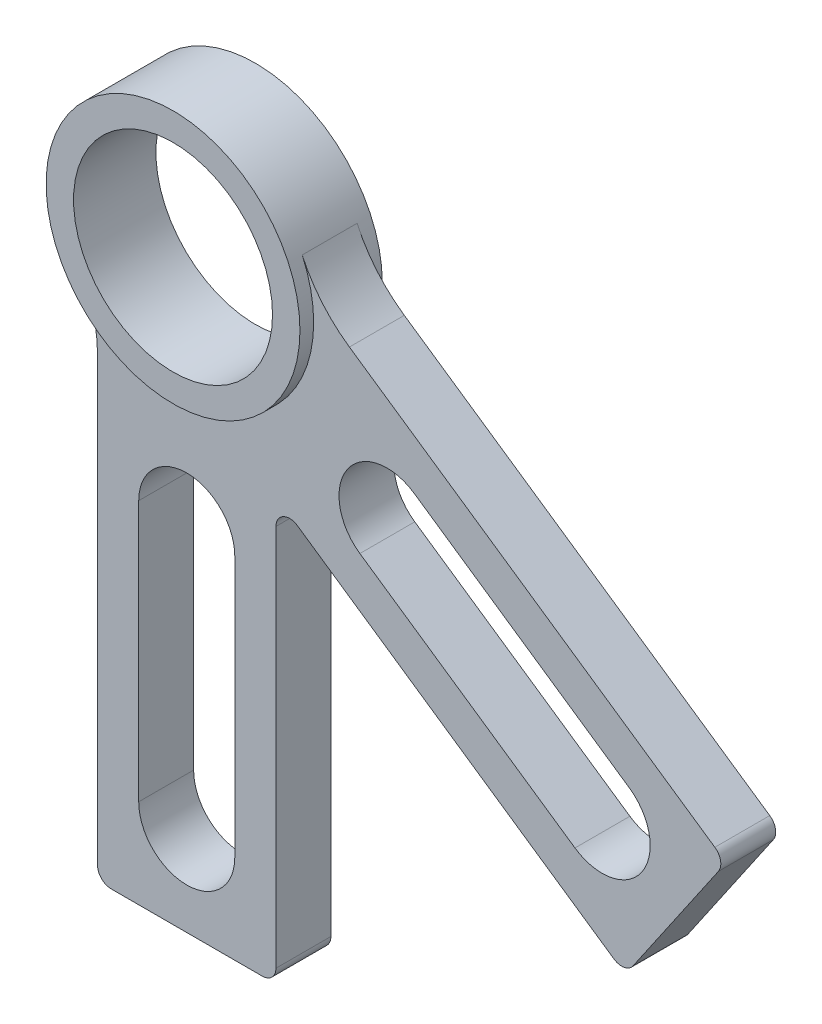
SolidWorks part; units mm, degrees
material "AISI 4130 Steel, annealed at 865C"
ref_plane "X-Y Datum" through (0, 0, 0) normal (0, 0, 1) x (1, 0, 0)
ref_plane "X-Z Datum" through (0, 0, 0) normal (0, 1, 0) x (1, 0, 0)
ref_plane "Y-Z Datum" through (0, 0, 0) normal (1, 0, 0) x (0, 0, -1)
sketch "Sketch1" plane through (0, 0, 0) normal (0, 0, 1) x (1, 0, 0)
  line L0 (0, -58.1206) -> (0, -27.9581) construction
  line L1 (-5.5562, -58.1206) -> (-5.5562, -27.9581)
  line L2 (5.5562, -58.1206) -> (5.5562, -27.9581)
  line L3 (48.0436, -32.9331) -> (23.1651, -15.8793) construction
  line L4 (44.9021, -37.516) -> (20.0236, -20.4622)
  line L5 (51.1851, -28.3502) -> (26.3066, -11.2964)
  line L6 (-10.3187, -15.7343) -> (-10.3187, -68.4393)
  line L7 (-10.3187, -68.4393) -> (10.3187, -68.4393)
  line L10 (50.7205, -47.2784) -> (62.3889, -30.2562)
  line L11 (62.3889, -30.2562) -> (18.8122, -0.3851)
  line L12 (0, -58.1206) -> (0, 0) construction
  line L13 (0, 0) -> (48.0436, -32.9331) construction
  line L14 (0, -63.6768) -> (0, -68.4393) construction
  line L15 (52.6265, -36.0746) -> (56.5547, -38.7673) construction
  line L16 (38.7458, -19.8233) -> (41.4385, -15.8951) construction
  line L17 (-5.5562, -43.0393) -> (-10.3187, -43.0393) construction
  line L18 (-10.3187, -17.6393) -> (10.3187, -17.6393) construction
  line L19 (10.3187, -17.6393) -> (10.3187, -68.4393) construction
  line L20 (5.5562, -43.0393) -> (10.3187, -43.0393) construction
  line L21 (0, -22.4018) -> (0, -17.6393) construction
  line L22 (50.7205, -47.2784) -> (8.8198, -18.5561) construction
  line L23 (8.8198, -18.5561) -> (20.4882, -1.534) construction
  line L24 (32.4628, -28.9891) -> (29.7701, -32.9173) construction
  line L25 (18.5822, -12.7378) -> (14.654, -10.0451) construction
  line L30 (50.7205, -47.2784) -> (12.8038, -21.2872)
  line L32 (10.3187, -22.5965) -> (10.3187, -68.4393)
  circle A0 centre (0, 0) radius 11.5062
  arc A1 (-5.5562, -58.1206) -> (5.5562, -58.1206) centre (0, -58.1206) ccw
  arc A2 (5.5562, -27.9581) -> (-5.5562, -27.9581) centre (0, -27.9581) ccw
  arc A3 (44.9021, -37.516) -> (51.1851, -28.3502) centre (48.0436, -32.9331) ccw
  arc A4 (26.3066, -11.2964) -> (20.0236, -20.4622) centre (23.1651, -15.8793) ccw
  arc A5 (13.3511, 6.1062) -> (-12.5852, -7.5598) centre (0, 0) ccw
  arc A6 (18.8122, -0.3851) -> (13.3511, 6.1062) centre (27.7879, 12.7089) cw
  arc A7 (-10.3187, -15.7343) -> (-12.5852, -7.5598) centre (-26.1937, -15.7343) ccw
  arc A12 (12.8038, -21.2872) -> (10.3187, -22.5965) centre (11.9062, -22.5965) ccw
  arc A14 (-12.5852, -7.5598) -> (13.3511, 6.1062) centre (0, 0) ccw
  point P5 (0, -43.0393)
  point P11 (35.6043, -24.4062)
  point P24 (56.5547, -38.7673)
  point P31 (0, -68.4393)
  point P36 (10.3187, -19.5837)
  point P39 (52.6265, -36.0746)
  dimension "D1" = 23.0124
  dimension "D2" = 14.6812
  dimension "D8" = 15.875
  dimension "D9" = 55.57
  dimension "D10" = 1.5875
  dimension "D3" = 20.6375
  dimension "D4" = 4.7625
  dimension "D5" = 50.8
  dimension "D6" = 2.032
  dimension "D7" = 1.905
extrude "Boss-Extrude1" add sketch "Sketch1" along normal blind 4.7625 and the other way blind 4.7625 contours A5 A14 A0 | A14 A7 L6 L7 L32 L30 L10 L11 A6 A4 L5 A3 L4 A2 L2 A1 L1 region at (-9.877, -11.2104, 0) region at (-6.6501, 12.6211, 0)
extrude "Cut-Extrude1" cut sketch "Sketch1<8>" along direction (0, 0, 1) on the side against the normal blind 1.5875 from surface contours A14 A7 L6 L7 L32 L30 L10 L11 A6 A4 L5 A3 L4 A2 L2 A1 L1 region at (-9.877, -11.2104, 0) starting at face at (11.5062, 0, 4.7625)
sketch "Sketch1<8>" plane through (0, 0, 0) normal (0, 0, 1) x (1, 0, 0) same geometry as "Sketch1"
extrude "Cut-Extrude2" cut sketch "Sketch1<9>" along direction (0, 0, 1) on the side of the normal blind 1.5875 from surface contours A14 A7 L6 L7 L32 A12 L30 L10 L11 A6 A4 L5 A3 L4 A2 L2 A1 L1 region at (-9.877, -11.2104, 0) starting at face at (11.5062, 0, -4.7625)
sketch "Sketch1<9>" plane through (0, 0, 0) normal (0, 0, 1) x (1, 0, 0) same geometry as "Sketch1"
fillet "Fillet1" radius 1.5875 4 edges at (62.3889, -30.2562, 0) (50.7205, -47.2784, 0) (10.3187, -68.4393, 0) (-10.3187, -68.4393, 0)
sketch "Sketch2" plane through (0, 0, 4.7625) normal (0, 0, 1) x (1, 0, 0)
  point P0 (0, 0)
sketch "Sketch3" plane through (0, 0, -4.7625) normal (0, 0, -1) x (-1, 0, 0)
  point P0 (0, 0)
